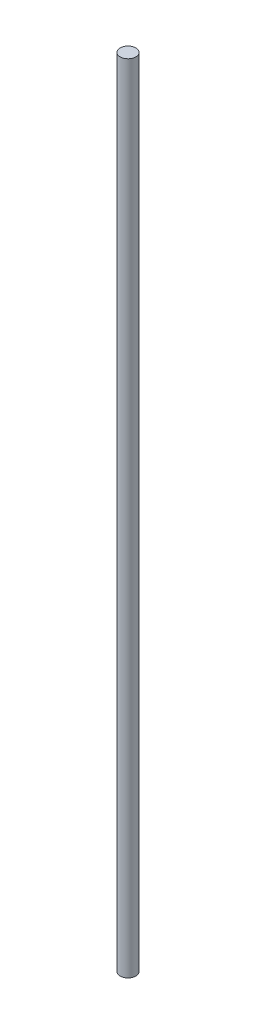
SolidWorks part; units mm, degrees
material "1060 Alloy"
ref_plane "Front Plane" through (0, 0, 0) normal (0, 0, 1) x (1, 0, 0)
ref_plane "Top Plane" through (0, 0, 0) normal (0, 1, 0) x (1, 0, 0)
ref_plane "Right Plane" through (0, 0, 0) normal (1, 0, 0) x (0, 0, -1)
sketch "Sketch1" plane through (0, 0, 0) normal (0, 1, 0) x (1, 0, 0)
  circle A0 centre (0, 0) radius 5
  dimension "D1" = 10
extrude "Boss-Extrude1" add sketch "Sketch1" along normal blind 509
equation "\"D1@Boss-Extrude1\"=450+59"
